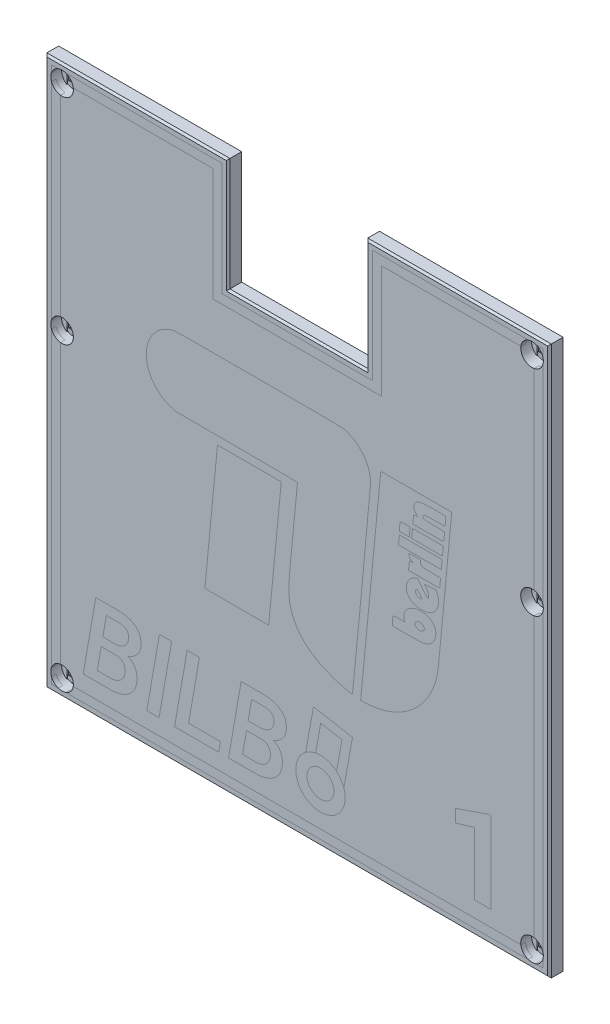
SolidWorks part; units mm, degrees
ref_plane "Front Plane" through (0, 0, 0) normal (0, 0, 1) x (1, 0, 0)
ref_plane "Top Plane" through (0, 0, 0) normal (0, 1, 0) x (1, 0, 0)
ref_plane "Right Plane" through (0, 0, 0) normal (1, 0, 0) x (0, 0, -1)
sketch "Sketch1" plane through (0, 0, 0) normal (0, 0, 1) x (1, 0, 0)
  line L0 (48, -68) -> (-48, -68) construction
  line L1 (56, -32.5) -> (56, -60) construction
  line L2 (56, 46) -> (56, -24.5) construction
  line L3 (-56, -24.5) -> (-56, 46) construction
  line L5 (-15, 54.4) -> (-15, 29) construction
  line L6 (-15, 29) -> (15, 29) construction
  line L8 (48, 54) -> (15, 54) construction
  line L9 (48, -68) -> (-48, -68) construction
  line L10 (56, -32.5) -> (56, -60) construction
  line L11 (56, 46) -> (56, -24.5) construction
  line L12 (-56, -24.5) -> (-56, 46) construction
  line L14 (-15, 54.4) -> (-15, 29) construction
  line L15 (-15, 29) -> (15, 29) construction
  line L16 (15, 29) -> (15, 54) construction
  line L17 (48, 54) -> (15, 54) construction
  line L18 (-15.25, 53.75) -> (-15.25, 28.75)
  line L19 (-55.75, 53.75) -> (-15.25, 53.75)
  line L20 (-55.75, 53.75) -> (-55.75, -67.75)
  line L21 (-55.75, -67.75) -> (55.875, -67.75)
  line L22 (55.875, 53.75) -> (55.875, -67.75)
  line L23 (-15.25, 28.75) -> (15.25, 28.75)
  line L24 (15.25, 28.75) -> (15.25, 53.75)
  line L25 (15.25, 53.75) -> (55.875, 53.75)
  circle A0 centre (-52, -64) radius 2.15 construction
  circle A3 centre (52, 50) radius 2.15 construction
  circle A4 centre (-52, 50) radius 2.15 construction
  circle A5 centre (-52, -64) radius 2.15 construction
  circle A6 centre (-52, 2.6) radius 2.15 construction
  circle A7 centre (52, 2.6) radius 2.15 construction
  circle A8 centre (52, 50) radius 2.15 construction
  circle A9 centre (-52, 50) radius 2.15 construction
  circle A10 centre (-52, 50) radius 1.35
  circle A11 centre (-52, 2.6) radius 1.35
  circle A12 centre (-52, -64) radius 1.35
  circle A13 centre (52, 50) radius 1.35
  circle A14 centre (52, 2.6) radius 1.35
  circle A15 centre (52, -64) radius 1.35
  circle A16 centre (-52, 2.6) radius 2.15 construction
  circle A17 centre (52, 2.6) radius 2.15 construction
  dimension "D5" = 2.7
  dimension "D1" = 0.25
  dimension "D2" = 0.25
  dimension "D3" = 0.25
  dimension "D4" = 0.25
  dimension "D6" = 0.25
  dimension "D7" = 0.25
  dimension "D8" = 0.25
extrude "Boss-Extrude1" add sketch "Sketch1" along normal blind 3
sketch "Sketch2" plane through (0, 0, 3) normal (0, 0, 1) x (1, 0, 0)
  line L5 (15.25, 28.75) -> (-15.25, 28.75) construction
  line L8 (-45.5, -63.25) -> (45.5, -63.25)
  line L9 (-45.5, -63.25) -> (-45.5, 27.75)
  line L10 (-45.5, 27.75) -> (45.5, 27.75)
  line L11 (45.5, -63.25) -> (45.5, 27.75)
  line L31 (-42, 24.25) -> (-28, 24.25)
  line L32 (-42, 24.25) -> (-42, 10.25)
  line L33 (-42, 10.25) -> (-28, 10.25)
  line L34 (-28, 24.25) -> (-28, 10.25)
  line L35 (-28, 24.25) -> (-14, 24.25)
  line L36 (-28, 24.25) -> (-28, 10.25)
  line L37 (-28, 10.25) -> (-14, 10.25)
  line L38 (-14, 24.25) -> (-14, 10.25)
  line L39 (-14, 24.25) -> (0, 24.25)
  line L40 (-14, 24.25) -> (-14, 10.25)
  line L41 (-14, 10.25) -> (0, 10.25)
  line L42 (0, 24.25) -> (0, 10.25)
  line L43 (0, 24.25) -> (14, 24.25)
  line L44 (0, 24.25) -> (0, 10.25)
  line L45 (0, 10.25) -> (14, 10.25)
  line L46 (14, 24.25) -> (14, 10.25)
  line L47 (14, 24.25) -> (28, 24.25)
  line L48 (14, 24.25) -> (14, 10.25)
  line L49 (14, 10.25) -> (28, 10.25)
  line L50 (28, 24.25) -> (28, 10.25)
  line L51 (28, 24.25) -> (42, 24.25)
  line L52 (28, 24.25) -> (28, 10.25)
  line L53 (28, 10.25) -> (42, 10.25)
  line L54 (42, 24.25) -> (42, 10.25)
  line L55 (-42, 10.25) -> (-28, 10.25)
  line L56 (-42, 10.25) -> (-42, -3.75)
  line L57 (-42, -3.75) -> (-28, -3.75)
  line L58 (-28, 10.25) -> (-28, -3.75)
  line L59 (-28, -3.75) -> (-14, -3.75)
  line L60 (-28, -3.75) -> (-28, 10.25)
  line L61 (-28, 10.25) -> (-14, 10.25)
  line L62 (-14, -3.75) -> (-14, 10.25)
  line L63 (-14, -3.75) -> (0, -3.75)
  line L64 (-14, -3.75) -> (-14, 10.25)
  line L65 (-14, 10.25) -> (0, 10.25)
  line L66 (0, -3.75) -> (0, 10.25)
  line L67 (0, -3.75) -> (14, -3.75)
  line L68 (0, -3.75) -> (0, 10.25)
  line L69 (0, 10.25) -> (14, 10.25)
  line L70 (14, -3.75) -> (14, 10.25)
  line L71 (14, -3.75) -> (28, -3.75)
  line L72 (14, -3.75) -> (14, 10.25)
  line L73 (14, 10.25) -> (28, 10.25)
  line L74 (28, -3.75) -> (28, 10.25)
  line L75 (28, -3.75) -> (42, -3.75)
  line L76 (28, -3.75) -> (28, 10.25)
  line L77 (28, 10.25) -> (42, 10.25)
  line L78 (42, -3.75) -> (42, 10.25)
  line L79 (42, -3.75) -> (28, -3.75)
  line L80 (42, -3.75) -> (42, -17.75)
  line L81 (42, -17.75) -> (28, -17.75)
  line L82 (28, -3.75) -> (28, -17.75)
  line L83 (14, -3.75) -> (28, -3.75)
  line L84 (14, -3.75) -> (14, -17.75)
  line L85 (14, -17.75) -> (28, -17.75)
  line L86 (28, -3.75) -> (28, -17.75)
  line L87 (0, -3.75) -> (14, -3.75)
  line L88 (0, -3.75) -> (0, -17.75)
  line L89 (0, -17.75) -> (14, -17.75)
  line L90 (14, -3.75) -> (14, -17.75)
  line L91 (-14, -3.75) -> (0, -3.75)
  line L92 (-14, -3.75) -> (-14, -17.75)
  line L93 (-14, -17.75) -> (0, -17.75)
  line L94 (0, -3.75) -> (0, -17.75)
  line L95 (-28, -3.75) -> (-14, -3.75)
  line L96 (-28, -3.75) -> (-28, -17.75)
  line L97 (-28, -17.75) -> (-14, -17.75)
  line L98 (-14, -3.75) -> (-14, -17.75)
  line L99 (-42, -3.75) -> (-28, -3.75)
  line L100 (-42, -3.75) -> (-42, -17.75)
  line L101 (-42, -17.75) -> (-28, -17.75)
  line L102 (-28, -3.75) -> (-28, -17.75)
  line L103 (-42, -17.75) -> (-28, -17.75)
  line L104 (-42, -17.75) -> (-42, -31.75)
  line L105 (-42, -31.75) -> (-28, -31.75)
  line L106 (-28, -17.75) -> (-28, -31.75)
  line L107 (-28, -31.75) -> (-14, -31.75)
  line L108 (-28, -31.75) -> (-28, -17.75)
  line L109 (-28, -17.75) -> (-14, -17.75)
  line L110 (-14, -31.75) -> (-14, -17.75)
  line L111 (-14, -17.75) -> (0, -17.75)
  line L112 (-14, -17.75) -> (-14, -31.75)
  line L113 (-14, -31.75) -> (0, -31.75)
  line L114 (0, -17.75) -> (0, -31.75)
  line L115 (0, -31.75) -> (14, -31.75)
  line L116 (0, -31.75) -> (0, -17.75)
  line L117 (0, -17.75) -> (14, -17.75)
  line L118 (14, -31.75) -> (14, -17.75)
  line L119 (14, -31.75) -> (28, -31.75)
  line L120 (14, -31.75) -> (14, -17.75)
  line L121 (14, -17.75) -> (28, -17.75)
  line L122 (28, -31.75) -> (28, -17.75)
  line L123 (28, -31.75) -> (42, -31.75)
  line L124 (28, -31.75) -> (28, -17.75)
  line L125 (28, -17.75) -> (42, -17.75)
  line L126 (42, -31.75) -> (42, -17.75)
  line L127 (-42, -31.75) -> (-28, -31.75)
  line L128 (-42, -31.75) -> (-42, -45.75)
  line L129 (-42, -45.75) -> (-28, -45.75)
  line L130 (-28, -31.75) -> (-28, -45.75)
  line L131 (-28, -45.75) -> (-14, -45.75)
  line L132 (-28, -45.75) -> (-28, -31.75)
  line L133 (-28, -31.75) -> (-14, -31.75)
  line L134 (-14, -45.75) -> (-14, -31.75)
  line L135 (-14, -45.75) -> (0, -45.75)
  line L136 (-14, -45.75) -> (-14, -31.75)
  line L137 (-14, -31.75) -> (0, -31.75)
  line L138 (0, -45.75) -> (0, -31.75)
  line L139 (0, -45.75) -> (14, -45.75)
  line L140 (0, -45.75) -> (0, -31.75)
  line L141 (0, -31.75) -> (14, -31.75)
  line L142 (14, -45.75) -> (14, -31.75)
  line L143 (14, -45.75) -> (28, -45.75)
  line L144 (14, -45.75) -> (14, -31.75)
  line L145 (14, -31.75) -> (28, -31.75)
  line L146 (28, -45.75) -> (28, -31.75)
  line L147 (28, -45.75) -> (42, -45.75)
  line L148 (28, -45.75) -> (28, -31.75)
  line L149 (28, -31.75) -> (42, -31.75)
  line L150 (42, -45.75) -> (42, -31.75)
  line L151 (42, -45.75) -> (28, -45.75)
  line L152 (42, -45.75) -> (42, -59.75)
  line L153 (42, -59.75) -> (28, -59.75)
  line L154 (28, -45.75) -> (28, -59.75)
  line L155 (28, -59.75) -> (14, -59.75)
  line L156 (28, -59.75) -> (28, -45.75)
  line L157 (28, -45.75) -> (14, -45.75)
  line L158 (14, -59.75) -> (14, -45.75)
  line L159 (0, -45.75) -> (14, -45.75)
  line L160 (0, -45.75) -> (0, -59.75)
  line L161 (0, -59.75) -> (14, -59.75)
  line L162 (14, -45.75) -> (14, -59.75)
  line L163 (-14, -45.75) -> (0, -45.75)
  line L164 (-14, -45.75) -> (-14, -59.75)
  line L165 (-14, -59.75) -> (0, -59.75)
  line L166 (0, -45.75) -> (0, -59.75)
  line L167 (-28, -45.75) -> (-14, -45.75)
  line L168 (-28, -45.75) -> (-28, -59.75)
  line L169 (-28, -59.75) -> (-14, -59.75)
  line L170 (-14, -45.75) -> (-14, -59.75)
  line L171 (-42, -45.75) -> (-28, -45.75)
  line L172 (-42, -45.75) -> (-42, -59.75)
  line L173 (-42, -59.75) -> (-28, -59.75)
  line L174 (-28, -45.75) -> (-28, -59.75)
  point P3 (0, 27.75)
  point P58 (-45.5, -17.75)
  dimension "D1" = 1
  dimension "D2" = 91
  dimension "D3" = 14
sketch "Sketch3" plane through (0, 0, 3) normal (0, 0, 1) x (1, 0, 0)
  circle A0 centre (-52, 50) radius 2.5
  circle A1 centre (-52, 2.6) radius 2.5
  circle A2 centre (-52, -64) radius 2.5
  circle A3 centre (52, -64) radius 2.5
  circle A4 centre (52, 2.6) radius 2.5
  circle A5 centre (52, 50) radius 2.5
  dimension "D1" = 5
extrude "Cut-Extrude1" cut sketch "Sketch3" against normal blind 2.4
sketch "Sketch4" plane through (0, 0, 0) normal (0, 0, -1) x (-1, 0, 0)
  line L0 (-15.25, 28.75) -> (15.25, 28.75) construction
  line L1 (-45.75, -57.75) -> (45.75, -57.75)
  line L2 (-45.75, -57.75) -> (-45.75, 27.75)
  line L3 (-45.75, 27.75) -> (45.75, 27.75)
  line L4 (45.75, -57.75) -> (45.75, 27.75)
  line L5 (-45.75, -57.75) -> (45.75, 27.75) construction
  line L6 (-45.75, 27.75) -> (45.75, -57.75) construction
  line L7 (55.75, 53.75) -> (55.75, -67.75) construction
  line L8 (55.75, -67.75) -> (-55.875, -67.75) construction
  point P0 (0, -15)
  point P9 (0, 27.75)
  dimension "D1" = 1
  dimension "D2" = 10
  dimension "D3" = 10
extrude "Cut-Extrude2" cut sketch "Sketch4" against normal blind 1.5
sketch "Sketch5" plane through (0, 0, 0.6) normal (0, 0, 1) x (1, 0, 0)
  line L2 (-53.35, 47.8958) -> (-53.35, 52.1042)
  line L4 (-50.65, 47.8958) -> (-50.65, 52.1042)
  line L5 (-53.35, 47.8958) -> (-50.65, 52.1042) construction
  line L6 (-53.35, 52.1042) -> (-50.65, 47.8958) construction
  line L8 (-53.35, 0.4958) -> (-53.35, 4.7042)
  line L10 (-50.65, 0.4958) -> (-50.65, 4.7042)
  line L11 (-53.35, 0.4958) -> (-50.65, 4.7042) construction
  line L12 (-53.35, 4.7042) -> (-50.65, 0.4958) construction
  line L14 (-53.35, -66.1042) -> (-53.35, -61.8958)
  line L16 (-50.65, -66.1042) -> (-50.65, -61.8958)
  line L17 (-53.35, -66.1042) -> (-50.65, -61.8958) construction
  line L18 (-53.35, -61.8958) -> (-50.65, -66.1042) construction
  circle A0 centre (-52, 50) radius 2.5 construction
  circle A1 centre (-52, 50) radius 1.35 construction
  arc A2 (-50.65, 52.1042) -> (-53.35, 52.1042) centre (-52, 50) ccw
  arc A3 (-53.35, 47.8958) -> (-50.65, 47.8958) centre (-52, 50) ccw
  circle A4 centre (-52, 2.6) radius 2.5 construction
  circle A5 centre (-52, 2.6) radius 1.35 construction
  circle A6 centre (-52, 2.6) radius 2.5 construction
  arc A7 (-50.65, 4.7042) -> (-53.35, 4.7042) centre (-52, 2.6) ccw
  arc A8 (-53.35, 0.4958) -> (-50.65, 0.4958) centre (-52, 2.6) ccw
  circle A9 centre (-52, -64) radius 2.5 construction
  circle A10 centre (-52, -64) radius 1.35 construction
  circle A11 centre (-52, -64) radius 2.5 construction
  arc A12 (-50.65, -61.8958) -> (-53.35, -61.8958) centre (-52, -64) ccw
  arc A13 (-53.35, -66.1042) -> (-50.65, -66.1042) centre (-52, -64) ccw
  point P0 (-52, 50)
  point P10 (-52, 2.6)
  point P22 (-52, -64)
extrude "Cut-Extrude3" cut sketch "Sketch5" against normal blind 0.2
sketch "Sketch6" plane through (0, 0, 0.4) normal (0, 0, 1) x (1, 0, 0)
  line L0 (-50.65, -66.1042) -> (-50.65, -61.8958) construction
  line L1 (-53.35, -65.35) -> (-50.65, -65.35)
  line L2 (-53.35, -65.35) -> (-53.35, -62.65)
  line L3 (-53.35, -62.65) -> (-50.65, -62.65)
  line L4 (-50.65, -65.35) -> (-50.65, -62.65)
  line L5 (-53.35, -65.35) -> (-50.65, -62.65) construction
  line L6 (-53.35, -62.65) -> (-50.65, -65.35) construction
  line L7 (-50.65, 0.4958) -> (-50.65, 4.7042) construction
  line L8 (-53.35, 1.25) -> (-50.65, 1.25)
  line L9 (-53.35, 1.25) -> (-53.35, 3.95)
  line L10 (-53.35, 3.95) -> (-50.65, 3.95)
  line L11 (-50.65, 1.25) -> (-50.65, 3.95)
  line L12 (-53.35, 1.25) -> (-50.65, 3.95) construction
  line L13 (-53.35, 3.95) -> (-50.65, 1.25) construction
  line L14 (-50.65, 47.8958) -> (-50.65, 52.1042) construction
  line L15 (-53.35, 48.65) -> (-50.65, 48.65)
  line L16 (-53.35, 48.65) -> (-53.35, 51.35)
  line L17 (-53.35, 51.35) -> (-50.65, 51.35)
  line L18 (-50.65, 48.65) -> (-50.65, 51.35)
  line L19 (-53.35, 48.65) -> (-50.65, 51.35) construction
  line L20 (-53.35, 51.35) -> (-50.65, 48.65) construction
  arc A0 (-50.65, -64) -> (-53.35, -64) centre (-52, -64) ccw construction
  arc A1 (-50.65, 2.6) -> (-53.35, 2.6) centre (-52, 2.6) ccw construction
  arc A2 (-50.65, 50) -> (-53.35, 50) centre (-52, 50) ccw construction
  point P0 (-52, -64)
  point P11 (-52, 2.6)
  point P22 (-52, 50)
extrude "Cut-Extrude4" cut sketch "Sketch6" against normal blind 0.2
mirror "Mirror1" about plane through (0, 0, 0) normal (1, 0, 0) of "Cut-Extrude4", "Cut-Extrude3"
chamfer "Chamfer1" distance 0.4 angle 45 8 edges at (0.0625, -67.75, 3) (55.875, -7, 3) (35.5625, 53.75, 3) (15.25, 41.25, 3) (0, 28.75, 3) (-15.25, 41.25, 3) (-35.5, 53.75, 3) (-55.75, -7, 3)
sketch "Sketch8" plane through (0, 0, 3) normal (0, 0, 1) x (1, 0, 0)
  line L16 (-54.35, 52.35) -> (-54.35, -66.35)
  line L17 (-54.35, -66.35) -> (54.475, -66.35)
  line L18 (54.475, -66.35) -> (54.475, 52.35)
  line L19 (54.475, 52.35) -> (16.65, 52.35)
  line L20 (16.65, 52.35) -> (16.65, 27.35)
  line L21 (16.65, 27.35) -> (-16.65, 27.35)
  line L22 (-16.65, 27.35) -> (-16.65, 52.35)
  line L23 (-16.65, 52.35) -> (-54.35, 52.35)
  line L24 (-54.35, 52.35) -> (-54.35, -66.35)
  line L25 (-54.35, -66.35) -> (54.475, -66.35)
  line L26 (54.475, -66.35) -> (54.475, 52.35)
  line L27 (54.475, 52.35) -> (16.65, 52.35)
  line L28 (16.65, 52.35) -> (16.65, 27.35)
  line L29 (16.65, 27.35) -> (-16.65, 27.35)
  line L30 (-16.65, 27.35) -> (-16.65, 52.35)
  line L31 (-16.65, 52.35) -> (-54.35, 52.35)
  line L40 (-52.35, 50.35) -> (-52.35, -64.35)
  line L41 (-52.35, -64.35) -> (52.475, -64.35)
  line L42 (52.475, -64.35) -> (52.475, 50.35)
  line L43 (52.475, 50.35) -> (18.65, 50.35)
  line L44 (18.65, 50.35) -> (18.65, 25.35)
  line L45 (18.65, 25.35) -> (-18.65, 25.35)
  line L46 (-18.65, 25.35) -> (-18.65, 50.35)
  line L47 (-18.65, 50.35) -> (-52.35, 50.35)
  line L48 (-52.35, 50.35) -> (-52.35, -64.35)
  line L49 (-52.35, -64.35) -> (52.475, -64.35)
  line L50 (52.475, -64.35) -> (52.475, 50.35)
  line L51 (52.475, 50.35) -> (18.65, 50.35)
  line L52 (18.65, 50.35) -> (18.65, 25.35)
  line L53 (18.65, 25.35) -> (-18.65, 25.35)
  line L54 (-18.65, 25.35) -> (-18.65, 50.35)
  line L55 (-18.65, 50.35) -> (-52.35, 50.35)
  dimension "D1" = 1
  dimension "D2" = 3
extrude "Cut-Extrude5" cut sketch "Sketch8" against normal blind 1
extrude "Boss-Extrude2" add sketch "Sketch8<2>" against normal up to surface (1 mm away) separate body up to face at (0, 43.0542, 2)
sketch "Sketch8<2>" plane through (0, 0, 3) normal (0, 0, 1) x (1, 0, 0) same geometry as "Sketch8"
sketch "Sketch9" plane through (0, 0, 3) normal (0, 0, 1) x (1, 0, 0)
  circle A0 centre (-52, 2.6) radius 2.5
  circle A1 centre (-52, 50) radius 2.5
  circle A2 centre (52, 50) radius 2.5
  circle A3 centre (52, 2.6) radius 2.5
  circle A4 centre (52, -64) radius 2.5
  circle A5 centre (-52, -64) radius 2.5
  arc A6 (-50.65, -61.8958) -> (-53.35, -61.8958) centre (-52, -64) ccw construction
extrude "Cut-Extrude6" cut sketch "Sketch9" against normal up to surface (2.4 mm away) up to face at (-50.075, 2.6, 0.6)
sketch "Sketch11" plane through (0, 2.9085, 3) normal (0, 0, 1) x (1, 0, 0)
  line L0 (18.5142, 7.7944) -> (18.5552, 7.9913)
  line L1 (18.5552, 7.9913) -> (26.3848, 7.9913)
  line L2 (26.3848, 7.9913) -> (34.2144, 7.9913)
  line L3 (34.2144, 7.9913) -> (34.2144, 7.7867)
  line L4 (15.3231, -38.0946) -> (14.0631, -38.1496)
  line L5 (14.0631, -38.1496) -> (14.117, -37.7198)
  line L6 (21.1299, -19.4619) -> (21.0705, -20.3587)
  line L7 (21.0705, -20.3587) -> (24.2694, -20.3587)
  line L8 (31.0012, -9.2197) -> (30.7192, -8.6245)
  line L9 (30.7192, -8.6245) -> (30.2137, -8.6712)
  line L10 (28.9389, -8.7714) -> (28.1696, -8.8251)
  line L11 (28.1696, -8.8251) -> (28.5188, -9.2039)
  line L12 (29.6785, -5.8166) -> (27.7239, -5.79)
  line L13 (27.7239, -5.79) -> (27.5129, -5.5445)
  line L14 (27.3019, -4.9539) -> (27.3019, -4.6087)
  line L15 (27.3019, -4.6087) -> (26.0217, -4.6087)
  line L16 (26.0217, -4.6087) -> (24.7415, -4.6087)
  line L17 (24.7415, -4.6087) -> (24.7927, -4.9242)
  line L18 (25.4435, -5.8283) -> (25.7706, -6.001)
  line L19 (25.7706, -6.001) -> (25.3175, -6.0049)
  line L20 (25.3175, -6.0049) -> (24.8645, -6.0088)
  line L21 (24.8645, -6.0088) -> (24.8144, -6.4901)
  line L22 (24.7143, -7.4526) -> (24.6643, -7.9338)
  line L23 (24.6643, -7.9338) -> (28.1138, -7.9338)
  line L24 (28.1138, -7.9338) -> (31.5634, -7.9338)
  line L25 (31.5634, -7.9338) -> (31.6633, -6.9531)
  line L26 (32.0823, -2.6181) -> (32.1345, -2.1587)
  line L27 (32.1345, -2.1587) -> (27.4092, -2.1587)
  line L28 (27.4092, -2.1587) -> (22.6838, -2.1587)
  line L29 (22.6838, -2.1587) -> (22.6344, -2.4431)
  line L30 (22.5259, -3.4494) -> (22.4668, -4.1712)
  line L31 (22.4668, -4.1712) -> (27.1918, -4.1712)
  line L32 (27.1918, -4.1712) -> (31.9168, -4.1712)
  line L33 (31.9168, -4.1712) -> (31.9734, -3.6244)
  line L34 (22.7029, -0.6494) -> (22.6418, -1.4587)
  line L35 (22.6418, -1.4587) -> (23.7355, -1.4587)
  line L36 (23.7355, -1.4587) -> (24.8293, -1.4587)
  line L37 (24.8293, -1.4587) -> (24.8904, -0.6494)
  line L38 (32.3448, 0.0944) -> (32.397, 0.5538)
  line L39 (32.397, 0.5538) -> (28.9845, 0.5538)
  line L40 (28.9845, 0.5538) -> (25.572, 0.5538)
  line L41 (25.572, 0.5538) -> (25.5198, 0.0944)
  line L42 (25.4109, -0.9119) -> (25.3543, -1.4587)
  line L43 (25.3543, -1.4587) -> (28.7668, -1.4587)
  line L44 (28.7668, -1.4587) -> (32.1793, -1.4587)
  line L45 (32.1793, -1.4587) -> (32.2359, -0.9119)
  line L46 (32.6048, 2.8451) -> (32.6624, 3.4302)
  line L47 (32.6624, 3.4302) -> (30.4286, 3.4576)
  line L48 (30.4228, 4.4913) -> (32.7706, 4.535)
  line L49 (32.7706, 4.535) -> (32.8612, 5.5293)
  line L50 (26.4105, 3.6819) -> (26.7249, 3.3537)
  line L51 (26.7249, 3.3537) -> (26.2797, 3.3537)
  line L52 (26.2797, 3.3537) -> (25.8345, 3.3537)
  line L53 (25.8345, 3.3537) -> (25.7807, 2.8725)
  line L54 (25.673, 1.91) -> (25.6192, 1.4287)
  line L55 (25.6192, 1.4287) -> (29.0305, 1.4287)
  line L56 (29.0305, 1.4287) -> (32.4418, 1.4287)
  line L57 (32.4418, 1.4287) -> (32.4945, 1.8444)
  line L58 (-13.32, -3.2742) -> (-26.7294, -3.2458)
  line L59 (-26.7294, -3.2458) -> (-27.4731, -3.0505)
  line L60 (-17.6232, -5.2431) -> (-17.5823, -5.0462)
  line L61 (-17.5823, -5.0462) -> (-10.5301, -5.0462)
  line L62 (-10.5301, -5.0462) -> (-3.478, -5.0462)
  line L63 (-3.478, -5.0462) -> (-3.5311, -5.5056)
  line L64 (-6.2596, -33.7244) -> (-6.3015, -33.9212)
  line L65 (-6.3015, -33.9212) -> (-13.3548, -33.9212)
  line L66 (-13.3548, -33.9212) -> (-20.4082, -33.9212)
  line L67 (-20.4082, -33.9212) -> (-20.3565, -33.5056)
  spline S0 degree 3 poles (14.117, -37.7198) (14.1467, -37.4834) (15.139, -27.1903) (16.3221, -14.8462) knots 0 0 0 0 1 1 1 1
  spline S1 degree 3 poles (16.3221, -14.8462) (17.5053, -2.5022) (18.4917, 7.6861) (18.5142, 7.7944) knots 0 0 0 0 1 1 1 1
  spline S2 degree 3 poles (34.2144, 7.7867) (34.2144, 7.6743) (33.5663, 0.8329) (32.7743, -7.4164) knots 0 0 0 0 1 1 1 1
  spline S3 degree 3 poles (32.7743, -7.4164) (31.9823, -15.6656) (31.3109, -22.6906) (31.2824, -23.0275) knots 0 0 0 0 1 1 1 1
  spline S4 degree 3 poles (31.2824, -23.0275) (30.8883, -27.6857) (28.463, -32.018) (24.6687, -34.8418) knots 0 0 0 0 1 1 1 1
  spline S5 degree 3 poles (24.6687, -34.8418) (21.9579, -36.8593) (18.8516, -37.9404) (15.3231, -38.0946) knots 0 0 0 0 1 1 1 1
  spline S6 degree 3 poles (27.9319, -20.2612) (29.5408, -19.9228) (30.6255, -18.7352) (30.7016, -17.2286) knots 0 0 0 0 1 1 1 1
  spline S7 degree 3 poles (30.7016, -17.2286) (30.7423, -16.4209) (30.5667, -15.924) (30.0421, -15.3632) knots 0 0 0 0 1 1 1 1
  spline S8 degree 3 poles (30.0421, -15.3632) (29.57, -14.8584) (28.8594, -14.5286) (27.9811, -14.4064) knots 0 0 0 0 1 1 1 1
  spline S9 degree 3 poles (27.9811, -14.4064) (25.8237, -14.1063) (23.6192, -15.5237) (23.63, -17.204) knots 0 0 0 0 1 1 1 1
  spline S10 degree 3 poles (23.63, -17.204) (23.6317, -17.4713) (23.6893, -17.7884) (23.7581, -17.9087) knots 0 0 0 0 1 1 1 1
  spline S11 degree 3 poles (23.7581, -17.9087) (23.8269, -18.0291) (23.8846, -18.157) (23.8863, -18.1931) knots 0 0 0 0 1 1 1 1
  spline S12 degree 3 poles (23.8863, -18.1931) (23.888, -18.2292) (23.3014, -18.2587) (22.5828, -18.2587) knots 0 0 0 0 1 1 1 1
  spline S13 degree 3 poles (22.5828, -18.2587) (21.0653, -18.2587) (21.218, -18.1322) (21.1299, -19.4619) knots 0 0 0 0 1 1 1 1
  spline S14 degree 3 poles (24.2694, -20.3587) (26.2855, -20.3587) (27.6397, -20.3227) (27.9319, -20.2612) knots 0 0 0 0 1 1 1 1
  spline S15 degree 3 poles (26.5356, -18.1328) (26.0167, -17.8986) (25.9669, -17.303) (26.4334, -16.9104) knots 0 0 0 0 1 1 1 1
  spline S16 degree 3 poles (26.4334, -16.9104) (27.1809, -16.2814) (28.4197, -16.7967) (28.1281, -17.6154) knots 0 0 0 0 1 1 1 1
  spline S17 degree 3 poles (28.1281, -17.6154) (27.9444, -18.1312) (27.1232, -18.398) (26.5356, -18.1328) knots 0 0 0 0 1 1 1 1
  spline S18 degree 3 poles (28.8968, -13.877) (29.9326, -13.5281) (30.6721, -12.8902) (31.0875, -11.9876) knots 0 0 0 0 1 1 1 1
  spline S19 degree 3 poles (31.0875, -11.9876) (31.2471, -11.6407) (31.2821, -11.4083) (31.2825, -10.69) knots 0 0 0 0 1 1 1 1
  spline S20 degree 3 poles (31.2825, -10.69) (31.2831, -9.8852) (31.2605, -9.7672) (31.0012, -9.2197) knots 0 0 0 0 1 1 1 1
  spline S21 degree 3 poles (30.2137, -8.6712) (29.9356, -8.6968) (29.3619, -8.742) (28.9389, -8.7714) knots 0 0 0 0 1 1 1 1
  spline S22 degree 3 poles (28.5188, -9.2039) (28.9238, -9.6432) (29.1884, -10.4009) (29.1006, -10.8693) knots 0 0 0 0 1 1 1 1
  spline S23 degree 3 poles (29.1006, -10.8693) (29.0701, -11.032) (29.0131, -11.1849) (28.974, -11.209) knots 0 0 0 0 1 1 1 1
  spline S24 degree 3 poles (28.974, -11.209) (28.9349, -11.2332) (28.4001, -10.6341) (27.7856, -9.8777) knots 0 0 0 0 1 1 1 1
  spline S25 degree 3 poles (27.7856, -9.8777) (27.171, -9.1213) (26.6361, -8.4902) (26.5969, -8.4752) knots 0 0 0 0 1 1 1 1
  spline S26 degree 3 poles (26.5969, -8.4752) (26.4445, -8.4169) (25.5094, -8.9548) (25.1086, -9.3314) knots 0 0 0 0 1 1 1 1
  spline S27 degree 3 poles (25.1086, -9.3314) (24.4964, -9.9065) (24.1969, -10.5966) (24.1962, -11.4337) knots 0 0 0 0 1 1 1 1
  spline S28 degree 3 poles (24.1962, -11.4337) (24.1957, -11.9976) (24.232, -12.1557) (24.4541, -12.5566) knots 0 0 0 0 1 1 1 1
  spline S29 degree 3 poles (24.4541, -12.5566) (25.0091, -13.5586) (25.9967, -14.036) (27.5452, -14.0509) knots 0 0 0 0 1 1 1 1
  spline S30 degree 3 poles (27.5452, -14.0509) (28.152, -14.0567) (28.4938, -14.0128) (28.8968, -13.877) knots 0 0 0 0 1 1 1 1
  spline S31 degree 3 poles (26.7331, -11.925) (26.5887, -11.862) (26.4136, -11.742) (26.3441, -11.6582) knots 0 0 0 0 1 1 1 1
  spline S32 degree 3 poles (26.3441, -11.6582) (26.167, -11.4448) (26.2, -10.9218) (26.4033, -10.7184) knots 0 0 0 0 1 1 1 1
  spline S33 degree 3 poles (26.4033, -10.7184) (26.5691, -10.5526) (26.5788, -10.5593) (27.1116, -11.2035) knots 0 0 0 0 1 1 1 1
  spline S34 degree 3 poles (27.1116, -11.2035) (27.4088, -11.5627) (27.6519, -11.8993) (27.6519, -11.9514) knots 0 0 0 0 1 1 1 1
  spline S35 degree 3 poles (27.6519, -11.9514) (27.6519, -12.0818) (27.0534, -12.0646) (26.7331, -11.925) knots 0 0 0 0 1 1 1 1
  spline S36 degree 3 poles (31.6633, -6.9531) (31.7182, -6.4138) (31.7339, -5.9434) (31.6981, -5.9078) knots 0 0 0 0 1 1 1 1
  spline S37 degree 3 poles (31.6981, -5.9078) (31.6624, -5.8723) (30.7535, -5.8312) (29.6785, -5.8166) knots 0 0 0 0 1 1 1 1
  spline S38 degree 3 poles (27.5129, -5.5445) (27.367, -5.3748) (27.3019, -5.1924) (27.3019, -4.9539) knots 0 0 0 0 1 1 1 1
  spline S39 degree 3 poles (24.7927, -4.9242) (24.8626, -5.3553) (25.0557, -5.6236) (25.4435, -5.8283) knots 0 0 0 0 1 1 1 1
  spline S40 degree 3 poles (24.8144, -6.4901) (24.7869, -6.7547) (24.7418, -7.1879) (24.7143, -7.4526) knots 0 0 0 0 1 1 1 1
  spline S41 degree 3 poles (31.9734, -3.6244) (32.0046, -3.3236) (32.0536, -2.8708) (32.0823, -2.6181) knots 0 0 0 0 1 1 1 1
  spline S42 degree 3 poles (22.6344, -2.4431) (22.6073, -2.5995) (22.5584, -3.0523) (22.5259, -3.4494) knots 0 0 0 0 1 1 1 1
  spline S43 degree 3 poles (24.8904, -0.6494) (24.9241, -0.2042) (24.9728, 0.2486) (24.9987, 0.3569) knots 0 0 0 0 1 1 1 1
  spline S44 degree 3 poles (24.9987, 0.3569) (25.0457, 0.5531) (25.042, 0.5538) (23.9521, 0.5538) knots 0 0 0 0 1 1 1 1
  spline S45 degree 3 poles (23.9521, 0.5538) (22.6812, 0.5538) (22.8027, 0.6708) (22.7029, -0.6494) knots 0 0 0 0 1 1 1 1
  spline S46 degree 3 poles (32.2359, -0.9119) (32.2671, -0.6111) (32.3161, -0.1583) (32.3448, 0.0944) knots 0 0 0 0 1 1 1 1
  spline S47 degree 3 poles (25.5198, 0.0944) (25.4911, -0.1583) (25.4421, -0.6111) (25.4109, -0.9119) knots 0 0 0 0 1 1 1 1
  spline S48 degree 3 poles (32.4945, 1.8444) (32.5235, 2.073) (32.5732, 2.5233) (32.6048, 2.8451) knots 0 0 0 0 1 1 1 1
  spline S49 degree 3 poles (30.4286, 3.4576) (28.3769, 3.4828) (28.1799, 3.4986) (28.0109, 3.6517) knots 0 0 0 0 1 1 1 1
  spline S50 degree 3 poles (28.0109, 3.6517) (27.7961, 3.8462) (27.7776, 4.0403) (27.9509, 4.2777) knots 0 0 0 0 1 1 1 1
  spline S51 degree 3 poles (27.9509, 4.2777) (28.0669, 4.4365) (28.2274, 4.4503) (30.4228, 4.4913) knots 0 0 0 0 1 1 1 1
  spline S52 degree 3 poles (32.8612, 5.5293) (32.9345, 6.3347) (32.9299, 6.5321) (32.8366, 6.5679) knots 0 0 0 0 1 1 1 1
  spline S53 degree 3 poles (32.8366, 6.5679) (32.7733, 6.5922) (31.5907, 6.5926) (30.2085, 6.5689) knots 0 0 0 0 1 1 1 1
  spline S54 degree 3 poles (30.2085, 6.5689) (27.5295, 6.5228) (27.1342, 6.4668) (26.5147, 6.0452) knots 0 0 0 0 1 1 1 1
  spline S55 degree 3 poles (26.5147, 6.0452) (26.0945, 5.7592) (25.8887, 5.44) (25.8387, 4.997) knots 0 0 0 0 1 1 1 1
  spline S56 degree 3 poles (25.8387, 4.997) (25.7867, 4.5351) (25.9475, 4.1651) (26.4105, 3.6819) knots 0 0 0 0 1 1 1 1
  spline S57 degree 3 poles (25.7807, 2.8725) (25.7511, 2.6078) (25.7026, 2.1747) (25.673, 1.91) knots 0 0 0 0 1 1 1 1
  spline S58 degree 3 poles (10.9394, -37.6838) (4.5558, -36.2295) (0.6192, -33.4572) (-1.0508, -29.24) knots 0 0 0 0 1 1 1 1
  spline S59 degree 3 poles (-1.0508, -29.24) (-1.5618, -27.9496) (-1.7573, -26.884) (-1.8054, -25.1275) knots 0 0 0 0 1 1 1 1
  spline S60 degree 3 poles (-1.8054, -25.1275) (-1.8467, -23.6151) (-1.8099, -23.1543) (-0.8795, -13.535) knots 0 0 0 0 1 1 1 1
  spline S61 degree 3 poles (-0.8795, -13.535) (-0.3466, -8.0254) (0.0894, -3.4691) (0.0894, -3.41) knots 0 0 0 0 1 1 1 1
  spline S62 degree 3 poles (0.0894, -3.41) (0.0894, -3.3257) (-2.7938, -3.2965) (-13.32, -3.2742) knots 0 0 0 0 1 1 1 1
  spline S63 degree 3 poles (-27.4731, -3.0505) (-29.7301, -2.4578) (-31.5856, -0.945) (-32.5916, 1.1225) knots 0 0 0 0 1 1 1 1
  spline S64 degree 3 poles (-32.5916, 1.1225) (-33.1142, 2.1966) (-33.2528, 2.7681) (-33.3104, 4.0868) knots 0 0 0 0 1 1 1 1
  spline S65 degree 3 poles (-33.3104, 4.0868) (-33.367, 5.3821) (-33.2667, 6.1099) (-32.8877, 7.155) knots 0 0 0 0 1 1 1 1
  spline S66 degree 3 poles (-32.8877, 7.155) (-32.3872, 8.5347) (-31.3522, 9.8871) (-30.1286, 10.7603) knots 0 0 0 0 1 1 1 1
  spline S67 degree 3 poles (-30.1286, 10.7603) (-29.4588, 11.2382) (-28.324, 11.7702) (-27.5169, 11.9847) knots 0 0 0 0 1 1 1 1
  spline S68 degree 3 poles (-27.5169, 11.9847) (-26.929, 12.141) (-26.1664, 12.1475) (-8.5294, 12.1475) knots 0 0 0 0 1 1 1 1
  spline S69 degree 3 poles (-8.5294, 12.1475) (9.1076, 12.1475) (9.8702, 12.141) (10.4581, 11.9847) knots 0 0 0 0 1 1 1 1
  spline S70 degree 3 poles (10.4581, 11.9847) (11.2233, 11.7814) (12.3319, 11.2718) (13.006, 10.8136) knots 0 0 0 0 1 1 1 1
  spline S71 degree 3 poles (13.006, 10.8136) (13.7149, 10.3317) (14.7837, 9.1887) (15.2034, 8.4635) knots 0 0 0 0 1 1 1 1
  spline S72 degree 3 poles (15.2034, 8.4635) (15.9502, 7.1734) (16.2769, 5.9865) (16.2769, 4.5634) knots 0 0 0 0 1 1 1 1
  spline S73 degree 3 poles (16.2769, 4.5634) (16.2769, 3.8422) (12.4473, -36.7334) (12.2916, -37.6619) knots 0 0 0 0 1 1 1 1
  spline S74 degree 3 poles (12.2916, -37.6619) (12.2654, -37.8183) (12.1965, -37.9433) (12.1385, -37.9396) knots 0 0 0 0 1 1 1 1
  spline S75 degree 3 poles (12.1385, -37.9396) (12.0805, -37.9356) (11.5409, -37.8209) (10.9394, -37.6838) knots 0 0 0 0 1 1 1 1
  spline S76 degree 3 poles (-20.3565, -33.5056) (-20.3281, -33.277) (-19.7107, -26.8687) (-18.9845, -19.265) knots 0 0 0 0 1 1 1 1
  spline S77 degree 3 poles (-18.9845, -19.265) (-18.2583, -11.6612) (-17.6457, -5.3514) (-17.6232, -5.2431) knots 0 0 0 0 1 1 1 1
  spline S78 degree 3 poles (-3.5311, -5.5056) (-3.5603, -5.7583) (-4.1768, -12.1666) (-4.901, -19.7462) knots 0 0 0 0 1 1 1 1
  spline S79 degree 3 poles (-4.901, -19.7462) (-5.6253, -27.3259) (-6.2366, -33.6161) (-6.2596, -33.7244) knots 0 0 0 0 1 1 1 1
extrude "Cut-Extrude7" cut sketch "Sketch11" against normal blind 1 contours S75 S74 S73 S72 S71 S70 S69 S68 S67 S66 S65 S64 S63 L59 L58 S62 S61 S60 S59 S58 | S5 S4 S3 S2 L3 L2 L1 L0 S1 S0 L5 L4 S57 L53 L52 L51 L50 S56 S55 S54 S53 S52 L49 L48 S51 S50 S49 L47 L46 S48 L57 L56 L55 L54 S47 L41 L40 L39 L38 S46 L45 L44 L43 L42 S45 S44 S43 L37 | S79 S78 L63 L62 L61 L60 S77 S76 L67 L66 L65 L64 | S17 S16 S15 | S35 S34 S33 S32 S31 region at (22.9176, -12.6776, 3) region at (-20.0232, 0.3534, 3) region at (-11.9409, -16.5752, 3) region at (27.1412, -14.5309, 3) region at (26.8247, -8.525, 3)
extrude "Boss-Extrude3" add sketch "Sketch11<3>" against normal up to surface (1 mm away) separate body contours S79 S78 L63 L62 L61 L60 S77 S76 L67 L66 L65 L64 | S75 S74 S73 S72 S71 S70 S69 S68 S67 S66 S65 S64 S63 L59 L58 S62 S61 S60 S59 S58 | S5 S4 S3 S2 L3 L2 L1 L0 S1 S0 L5 L4 S57 L53 L52 L51 L50 S56 S55 S54 S53 S52 L49 L48 S51 S50 S49 L47 L46 S48 L57 L56 L55 L54 S47 L41 L40 L39 L38 S46 L45 L44 L43 L42 S45 S44 S43 L37 | S17 S16 S15 | S35 S34 S33 S32 S31 region at (22.9176, -12.6776, 3) region at (-20.0232, 0.3534, 3) region at (-11.9409, -16.5752, 3) region at (27.1412, -14.5309, 3) region at (26.8247, -8.525, 3) up to face at (-7.6448, -2.6402, 2)
sketch "Sketch11<3>" plane through (0, 2.9085, 3) normal (0, 0, 1) x (1, 0, 0) same geometry as "Sketch11"
sketch "Sketch12" plane through (0, 0, 3) normal (0, 0, 1) x (1, 0, 0)
  line L0 (3.6391, -41.6777) -> (12.2715, -43.2417)
  line L1 (12.2715, -43.2417) -> (10.3456, -53.8713)
  line L3 (1.896, -51.2984) -> (3.6391, -41.6777)
  line L4 (-47.3145, -60.8833) -> (-44.527, -44.8413)
  line L5 (-44.527, -44.8413) -> (-39.602, -44.8523)
  line L6 (-41.431, -60.8833) -> (-47.3145, -60.8833)
  line L7 (-43.3371, -53.6446) -> (-44.2075, -58.6577)
  line L8 (-44.2075, -58.6577) -> (-41.3539, -58.6687)
  line L9 (-40.0758, -53.6556) -> (-43.3371, -53.6446)
  line L10 (-42.9845, -51.5953) -> (-40.4834, -51.6063)
  line L11 (-39.3706, -47.1) -> (-42.2022, -47.089)
  line L12 (-42.2022, -47.089) -> (-42.9845, -51.5953)
  line L13 (-30.5343, -60.8833) -> (-33.2447, -60.8833)
  line L14 (-33.2447, -60.8833) -> (-30.4572, -44.8413)
  line L15 (-30.4572, -44.8413) -> (-27.7468, -44.8413)
  line L16 (-27.7468, -44.8413) -> (-30.5343, -60.8833)
  line L17 (-24.0007, -58.6577) -> (-16.9272, -58.6577)
  line L18 (-16.9272, -58.6577) -> (-17.3239, -60.8833)
  line L19 (-17.3239, -60.8833) -> (-27.1077, -60.8833)
  line L20 (-27.1077, -60.8833) -> (-24.3202, -44.8413)
  line L21 (-24.3202, -44.8413) -> (-21.5988, -44.8413)
  line L22 (-21.5988, -44.8413) -> (-24.0007, -58.6577)
  line L23 (-15.1533, -60.8833) -> (-12.3658, -44.8413)
  line L24 (-12.3658, -44.8413) -> (-7.4408, -44.8523)
  line L25 (-9.2698, -60.8833) -> (-15.1533, -60.8833)
  line L26 (-11.1759, -53.6446) -> (-12.0463, -58.6577)
  line L27 (-12.0463, -58.6577) -> (-9.1927, -58.6687)
  line L28 (-7.9146, -53.6556) -> (-11.1759, -53.6446)
  line L29 (-10.8233, -51.5953) -> (-8.3222, -51.6063)
  line L30 (-7.2094, -47.1) -> (-10.041, -47.089)
  line L31 (-10.041, -47.089) -> (-10.8233, -51.5953)
  spline S0 degree 3 poles (-39.602, -44.8523) (-37.8685, -44.8597) (-36.5684, -45.2379) (-35.7017, -45.9872) knots 0 0 0 0 1 1 1 1
  spline S1 degree 3 poles (-35.7017, -45.9872) (-34.8276, -46.729) (-34.442, -47.761) (-34.5448, -49.0832) knots 0 0 0 0 1 1 1 1
  spline S2 degree 3 poles (-34.5448, -49.0832) (-34.677, -50.6404) (-35.6282, -51.8119) (-37.3984, -52.5979) knots 0 0 0 0 1 1 1 1
  spline S3 degree 3 poles (-37.3984, -52.5979) (-36.7374, -52.8329) (-36.2269, -53.2626) (-35.867, -53.887) knots 0 0 0 0 1 1 1 1
  spline S4 degree 3 poles (-35.867, -53.887) (-35.507, -54.5113) (-35.3528, -55.2569) (-35.4042, -56.1236) knots 0 0 0 0 1 1 1 1
  spline S5 degree 3 poles (-35.4042, -56.1236) (-35.507, -57.5927) (-36.0983, -58.7532) (-37.1781, -59.6053) knots 0 0 0 0 1 1 1 1
  spline S6 degree 3 poles (-37.1781, -59.6053) (-38.2505, -60.4573) (-39.6681, -60.8833) (-41.431, -60.8833) knots 0 0 0 0 1 1 1 1
  spline S7 degree 3 poles (-41.3539, -58.6687) (-40.4945, -58.6687) (-39.7636, -58.441) (-39.1613, -57.9856) knots 0 0 0 0 1 1 1 1
  spline S8 degree 3 poles (-39.1613, -57.9856) (-38.559, -57.5302) (-38.2027, -56.9059) (-38.0926, -56.1126) knots 0 0 0 0 1 1 1 1
  spline S9 degree 3 poles (-38.0926, -56.1126) (-37.9897, -55.356) (-38.1036, -54.7647) (-38.4341, -54.3387) knots 0 0 0 0 1 1 1 1
  spline S10 degree 3 poles (-38.4341, -54.3387) (-38.7647, -53.9127) (-39.3119, -53.685) (-40.0758, -53.6556) knots 0 0 0 0 1 1 1 1
  spline S11 degree 3 poles (-40.4834, -51.6063) (-39.5873, -51.6063) (-38.8565, -51.3933) (-38.2909, -50.9673) knots 0 0 0 0 1 1 1 1
  spline S12 degree 3 poles (-38.2909, -50.9673) (-37.7253, -50.5412) (-37.3911, -49.9646) (-37.2883, -49.2374) knots 0 0 0 0 1 1 1 1
  spline S13 degree 3 poles (-37.2883, -49.2374) (-37.1046, -47.8639) (-37.7988, -47.1514) (-39.3706, -47.1) knots 0 0 0 0 1 1 1 1
  spline S14 degree 3 poles (-7.4408, -44.8523) (-5.7073, -44.8597) (-4.4072, -45.2379) (-3.5405, -45.9872) knots 0 0 0 0 1 1 1 1
  spline S15 degree 3 poles (-3.5405, -45.9872) (-2.6664, -46.729) (-2.2808, -47.761) (-2.3836, -49.0832) knots 0 0 0 0 1 1 1 1
  spline S16 degree 3 poles (-2.3836, -49.0832) (-2.5158, -50.6404) (-3.467, -51.8119) (-5.2372, -52.5979) knots 0 0 0 0 1 1 1 1
  spline S17 degree 3 poles (-5.2372, -52.5979) (-4.5762, -52.8329) (-4.0657, -53.2626) (-3.7057, -53.887) knots 0 0 0 0 1 1 1 1
  spline S18 degree 3 poles (-3.7057, -53.887) (-3.3458, -54.5113) (-3.1916, -55.2569) (-3.243, -56.1236) knots 0 0 0 0 1 1 1 1
  spline S19 degree 3 poles (-3.243, -56.1236) (-3.3458, -57.5927) (-3.9371, -58.7532) (-5.0169, -59.6053) knots 0 0 0 0 1 1 1 1
  spline S20 degree 3 poles (-5.0169, -59.6053) (-6.0893, -60.4573) (-7.5069, -60.8833) (-9.2698, -60.8833) knots 0 0 0 0 1 1 1 1
  spline S21 degree 3 poles (-9.1927, -58.6687) (-8.3333, -58.6687) (-7.6024, -58.441) (-7.0001, -57.9856) knots 0 0 0 0 1 1 1 1
  spline S22 degree 3 poles (-7.0001, -57.9856) (-6.3978, -57.5302) (-6.0415, -56.9059) (-5.9314, -56.1126) knots 0 0 0 0 1 1 1 1
  spline S23 degree 3 poles (-5.9314, -56.1126) (-5.8285, -55.356) (-5.9424, -54.7647) (-6.2729, -54.3387) knots 0 0 0 0 1 1 1 1
  spline S24 degree 3 poles (-6.2729, -54.3387) (-6.6034, -53.9127) (-7.1507, -53.685) (-7.9146, -53.6556) knots 0 0 0 0 1 1 1 1
  spline S25 degree 3 poles (-8.3222, -51.6063) (-7.4261, -51.6063) (-6.6953, -51.3933) (-6.1297, -50.9673) knots 0 0 0 0 1 1 1 1
  spline S26 degree 3 poles (-6.1297, -50.9673) (-5.5641, -50.5412) (-5.2299, -49.9646) (-5.127, -49.2374) knots 0 0 0 0 1 1 1 1
  spline S27 degree 3 poles (-5.127, -49.2374) (-4.9434, -47.8639) (-5.6375, -47.1514) (-7.2094, -47.1) knots 0 0 0 0 1 1 1 1
  spline S28 degree 3 poles (5.1875, -50.1938) (2.9807, -50.1938) (0.9912, -51.5231) (0.1467, -53.562) knots 0 0 0 0 1 1 1 1
  spline S29 degree 3 poles (0.1467, -53.562) (-0.6978, -55.6008) (-0.231, -57.9476) (1.3294, -59.508) knots 0 0 0 0 1 1 1 1
  spline S30 degree 3 poles (1.3294, -59.508) (2.8899, -61.0685) (5.2367, -61.5353) (7.2755, -60.6908) knots 0 0 0 0 1 1 1 1
  spline S31 degree 3 poles (7.2755, -60.6908) (9.3143, -59.8463) (10.6437, -57.8568) (10.6437, -55.6499) knots 0 0 0 0 1 1 1 1
  spline S32 degree 3 poles (10.6437, -55.6499) (10.6437, -54.2029) (10.0688, -52.8151) (9.0456, -51.7919) knots 0 0 0 0 1 1 1 1
  spline S33 degree 3 poles (9.0456, -51.7919) (8.0224, -50.7686) (6.6346, -50.1938) (5.1875, -50.1938) knots 0 0 0 0 1 1 1 1
  spline S34 degree 3 poles (5.1875, -52.6634) (3.9796, -52.6634) (2.8906, -53.391) (2.4283, -54.507) knots 0 0 0 0 1 1 1 1
  spline S35 degree 3 poles (2.4283, -54.507) (1.966, -55.623) (2.2215, -56.9076) (3.0757, -57.7618) knots 0 0 0 0 1 1 1 1
  spline S36 degree 3 poles (3.0757, -57.7618) (3.9298, -58.6159) (5.2144, -58.8714) (6.3304, -58.4092) knots 0 0 0 0 1 1 1 1
  spline S37 degree 3 poles (6.3304, -58.4092) (7.4464, -57.9469) (8.1741, -56.8579) (8.1741, -55.6499) knots 0 0 0 0 1 1 1 1
  spline S38 degree 3 poles (8.1741, -55.6499) (8.1741, -54.8579) (7.8594, -54.0982) (7.2993, -53.5381) knots 0 0 0 0 1 1 1 1
  spline S39 degree 3 poles (7.2993, -53.5381) (6.7392, -52.9781) (5.9796, -52.6634) (5.1875, -52.6634) knots 0 0 0 0 1 1 1 1
extrude "Cut-Extrude8" cut sketch "Sketch12" against normal blind 1 contours S32 S33 S28 S29 S30 S31 S39 S38 S37 S36 S35 S34 | S20 S19 S18 S17 S16 S15 S14 L24 L23 L25 S27 S26 S25 L29 L31 L30 S24 S23 S22 S21 L27 L26 L28 | L22 L21 L20 L19 L18 L17 | L16 L15 L14 L13 | S6 S5 S4 S3 S2 S1 S0 L5 L4 L6 S13 S12 S11 L10 L12 L11 S10 S9 S8 S7 L8 L7 L9 region at (3.5006, -50.6234, 3) region at (-40.9255, -52.9587, 3) region at (-30.4957, -52.8623, 3) region at (-23.3749, -54.6921, 3) region at (-8.7643, -52.9587, 3)
extrude "Boss-Extrude4" add sketch "Sketch12<3>" against normal up to surface (1 mm away) separate body contours S6 S5 S4 S3 S2 S1 S0 L5 L4 L6 S13 S12 S11 L10 L12 L11 S10 S9 S8 S7 L8 L7 L9 | L16 L15 L14 L13 | L22 L21 L20 L19 L18 L17 | S20 S19 S18 S17 S16 S15 S14 L24 L23 L25 S27 S26 S25 L29 L31 L30 S24 S23 S22 S21 L27 L26 L28 | S32 S33 S28 S29 S30 S31 S39 S38 S37 S36 S35 S34 region at (3.5006, -50.6234, 3) region at (-40.9255, -52.9587, 3) region at (-30.4957, -52.8623, 3) region at (-23.3749, -54.6921, 3) region at (-8.7643, -52.9587, 3) up to face at (-40.1961, -49.9747, 2)
sketch "Sketch12<3>" plane through (0, 0, 3) normal (0, 0, 1) x (1, 0, 0) same geometry as "Sketch12"
sketch "Sketch13" plane through (0, 0, 3) normal (0, 0, 1) x (1, 0, 0)
  line L0 (12.2715, -43.2417) -> (10.3456, -53.8713) construction
  line L1 (3.6391, -41.6777) -> (12.2715, -43.2417) construction
  line L2 (1.896, -51.2984) -> (3.6391, -41.6777) construction
  line L3 (12.2715, -43.2417) -> (10.3456, -53.8713)
  line L4 (3.6391, -41.6777) -> (12.2715, -43.2417)
  line L5 (1.896, -51.2984) -> (3.6391, -41.6777)
  line L6 (4.1092, -50.3012) -> (5.2505, -44.0022)
  line L7 (5.2505, -44.0022) -> (9.947, -44.8531)
  line L8 (9.947, -44.8531) -> (8.7409, -51.5096)
  spline S6 degree 3 poles (-1765.9504, 2349.9023) (1387.4767, -2750.3079) (-922.8197, 2827.1637) (453.8066, -3008.9668) knots -20.335414 -20.335414 -20.335414 -20.335414 21.335327 21.335327 21.335327 21.335327 only from (10.6437, -55.6499) to (9.0456, -51.7919)
  spline S7 degree 3 poles (-2948.1694, 392.9786) (2888.0046, -983.6625) (-2689.4399, 1326.6289) (2410.6817, -1826.7519) knots -20.335422 -20.335422 -20.335422 -20.335422 21.335256 21.335256 21.335256 21.335256 only from (9.0456, -51.7919) to (5.1875, -50.1938)
  spline S8 degree 3 poles (-2016.9495, -2253.8329) (2381.8067, 1823.4585) (-2640.3842, -1532.279) (2809.9299, 971.3867) knots -13.391063 -13.391063 -13.391063 -13.391063 14.391155 14.391155 14.391155 14.391155 only from (5.1875, -50.1938) to (0.1467, -53.562)
  spline S9 degree 3 poles (1262.2049, -2765.0709) (-821.3883, 2859.1653) (356.9966, -3064.9226) (129.6603, 2928.6255) knots -13.391072 -13.391072 -13.391072 -13.391072 14.391162 14.391162 14.391162 14.391162 only from (0.1467, -53.562) to (1.3294, -59.508)
  spline S10 degree 3 poles (2989.4043, 68.8251) (-3004.0318, 296.1509) (2919.9553, -882.2132) (-2704.1921, 1201.3521) knots -13.391072 -13.391072 -13.391072 -13.391072 14.391004 14.391004 14.391004 14.391004 only from (1.3294, -59.508) to (7.2755, -60.6908)
  spline S11 degree 3 poles (1032.2017, 2749.0436) (-1471.4161, -2701.1798) (1884.2693, 2320.9344) (-2192.9691, -2077.7585) knots -13.391072 -13.391072 -13.391072 -13.391072 14.391004 14.391004 14.391004 14.391004 only from (7.2755, -60.6908) to (10.6437, -55.6499)
  spline S12 degree 3 poles (10.6437, -55.6499) (10.6437, -54.2029) (10.0688, -52.8151) (9.0456, -51.7919) knots 0 0 0 0 1 1 1 1
  spline S13 degree 3 poles (9.0456, -51.7919) (8.0224, -50.7686) (6.6346, -50.1938) (5.1875, -50.1938) knots 0 0 0 0 1 1 1 1
  spline S14 degree 3 poles (5.1875, -50.1938) (2.9807, -50.1938) (0.9912, -51.5231) (0.1467, -53.562) knots 0 0 0 0 1 1 1 1
  spline S15 degree 3 poles (0.1467, -53.562) (-0.6978, -55.6008) (-0.231, -57.9476) (1.3294, -59.508) knots 0 0 0 0 1 1 1 1
  spline S16 degree 3 poles (1.3294, -59.508) (2.8899, -61.0685) (5.2367, -61.5353) (7.2755, -60.6908) knots 0 0 0 0 1 1 1 1
  spline S17 degree 3 poles (7.2755, -60.6908) (9.3143, -59.8463) (10.6437, -57.8568) (10.6437, -55.6499) knots 0 0 0 0 1 1 1 1
  dimension "D2" = 2
  dimension "D3" = 2
  dimension "D4" = 2
  dimension "D1" = 0
extrude "Cut-Extrude9" cut sketch "Sketch13" against normal blind 1 contours S14 L6 L7 L8 S13 S12 L3 L4 L5 region at (11.151, -48.528, 3)
extrude "Boss-Extrude5" add sketch "Sketch13<3>" against normal up to surface (1 mm away) separate body contours S14 L6 L7 L8 S13 S12 L3 L4 L5 region at (11.151, -48.528, 3) up to face at (5.5357, -51.6123, 2)
sketch "Sketch13<3>" plane through (0, 0, 3) normal (0, 0, 1) x (1, 0, 0) same geometry as "Sketch13"
sketch "Sketch14" plane through (0, 0, 3) normal (0, 0, 1) x (1, 0, 0)
  line L0 (33, -60.8833) -> (44.7706, -60.8833) construction
  text T0 "1" font "Roboto" height 18
  dimension "D1" = 33
extrude "Cut-Extrude10" cut sketch "Sketch14" against normal blind 1
extrude "Boss-Extrude6" add sketch "Sketch14<2>" against normal up to surface (1 mm away) separate body up to face at (39.5689, -49.7476, 2)
sketch "Sketch14<2>" plane through (0, 0, 3) normal (0, 0, 1) x (1, 0, 0) same geometry as "Sketch14"
